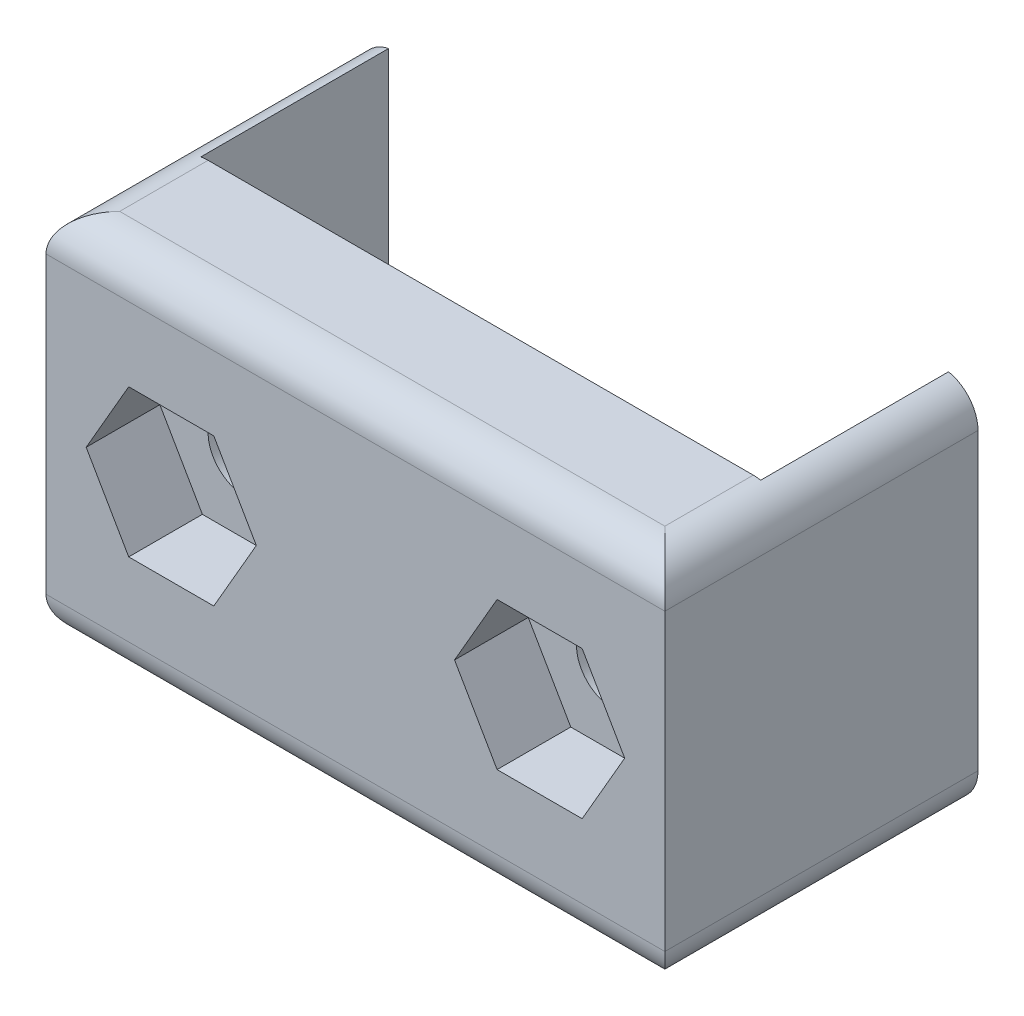
SolidWorks part; units mm, degrees
ref_plane "Front Plane" through (0, 0, 0) normal (0, 0, 1) x (1, 0, 0)
ref_plane "Top Plane" through (0, 0, 0) normal (0, 1, 0) x (1, 0, 0)
ref_plane "Right Plane" through (0, 0, 0) normal (1, 0, 0) x (0, 0, -1)
sketch "Sketch1" plane through (0, 0, 0) normal (0, 1, 0) x (1, 0, 0)
  line L0 (-21.336, 0) -> (21.336, 0)
  line L1 (-19.304, 12.954) -> (19.304, 12.954)
  line L2 (-19.304, 12.954) -> (-19.304, -12.954)
  line L3 (-19.304, -12.954) -> (19.304, -12.954)
  line L4 (19.304, 12.954) -> (19.304, -12.954)
  line L5 (-19.304, 12.954) -> (19.304, -12.954) construction
  line L6 (-19.304, -12.954) -> (19.304, 12.954) construction
  line L7 (-21.336, 21.59) -> (21.336, 21.59)
  line L8 (-21.336, 21.59) -> (-21.336, -21.59)
  line L9 (-21.336, -21.59) -> (21.336, -21.59)
  line L10 (21.336, 21.59) -> (21.336, -21.59)
  line L11 (-21.336, 21.59) -> (21.336, -21.59) construction
  line L12 (-21.336, -21.59) -> (21.336, 21.59) construction
  point P0 (0, 0)
  point P6 (0, 0)
  dimension "D1" = 38.608
  dimension "D2" = 25.908
  dimension "D3" = 42.672
  dimension "D4" = 43.18
extrude "Boss-Extrude1" add sketch "Sketch1" along normal blind 25.4 contours L10 L0 L4 L3 L2 L8 L9 region at (0, 0, 15.9226)
sketch "Sketch2" plane through (0, 0, 21.59) normal (0, 0, 1) x (1, 0, 0)
  line L0 (-21.336, 12.7) -> (21.336, 12.7) construction
  line L1 (-21.336, 25.4) -> (-21.336, 0) construction
  line L2 (21.336, 25.4) -> (21.336, 0) construction
  line L3 (-21.336, 0) -> (21.336, 0) construction
  circle A0 centre (-12.7, 12.7) radius 2.54
  circle A1 centre (12.7, 12.7) radius 2.54
  point P15 (0, 0)
  dimension "D1" = 5.08
  dimension "D2" = 5.08
  dimension "D3" = 12.7
  dimension "D4" = 12.7
extrude "Cut-Extrude1" cut sketch "Sketch2" against normal through all
sketch "Sketch3" plane through (0, 0, 21.59) normal (0, 0, 1) x (1, 0, 0)
  line L1 (-9.7671, 7.62) -> (-6.8341, 12.7)
  line L2 (-6.8341, 12.7) -> (-9.7671, 17.78)
  line L3 (-9.7671, 17.78) -> (-15.6329, 17.78)
  line L4 (-15.6329, 17.78) -> (-18.5659, 12.7)
  line L5 (-18.5659, 12.7) -> (-15.6329, 7.62)
  line L6 (-15.6329, 7.62) -> (-9.7671, 7.62)
  line L7 (15.6329, 7.62) -> (18.5659, 12.7)
  line L8 (18.5659, 12.7) -> (15.6329, 17.78)
  line L9 (15.6329, 17.78) -> (9.7671, 17.78)
  line L10 (9.7671, 17.78) -> (6.8341, 12.7)
  line L11 (6.8341, 12.7) -> (9.7671, 7.62)
  line L12 (9.7671, 7.62) -> (15.6329, 7.62)
  circle A4 centre (-12.7, 12.7) radius 5.08 construction
  circle A5 centre (-12.7, 12.7) radius 2.54 construction
  circle A6 centre (12.7, 12.7) radius 5.08 construction
  dimension "D1" = 10.16
  dimension "D2" = 10.16
extrude "Cut-Extrude2" cut sketch "Sketch3" against normal blind 5.08
fillet "Fillet1" radius 2.54 3 edges at (-21.336, 25.4, 10.795) (21.336, 25.4, 10.795) (0, 25.4, 21.59)
fillet "Fillet2" radius 2.54 3 edges at (-21.336, 0, 10.795) (0, 0, 21.59) (21.336, 0, 10.795)
